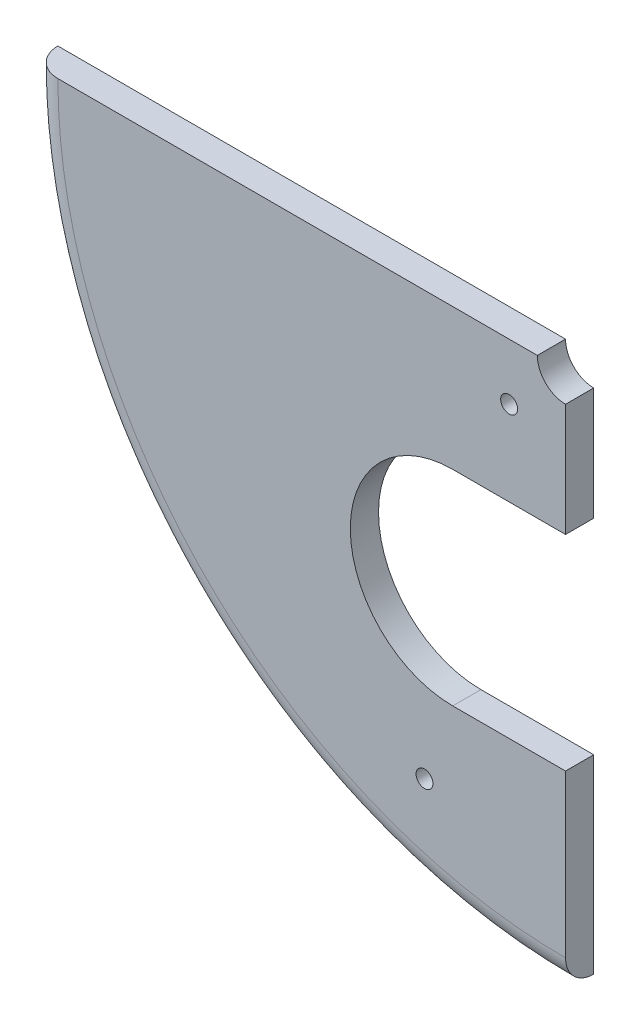
SolidWorks part; units mm, degrees
ref_plane "前基準面" through (0, 0, 0) normal (0, 0, 1) x (1, 0, 0)
ref_plane "上基準面" through (0, 0, 0) normal (0, 1, 0) x (1, 0, 0)
ref_plane "右基準面" through (0, 0, 0) normal (1, 0, 0) x (0, 0, -1)
sketch "草圖1" plane through (0, 0, 0) normal (0, 0, 1) x (1, 0, 0)
  line L0 (-95, 0) -> (-5, 0) construction
  line L1 (-5, 0) -> (-95, 0)
  line L2 (0, -5) -> (0, -95)
  line L3 (95, 0) -> (168.4046, 0) construction
  arc A0 (-95, 0) -> (0, -95) centre (0, 0) ccw
  circle A1 centre (-10, -10) radius 1.5
  arc A3 (-5, 0) -> (0, -5) centre (0, 0) ccw
  circle A4 centre (-25, -75) radius 1.5
  point P16 (0, 0)
  dimension "D1" = 190
  dimension "D2" = 3
  dimension "D9" = 5
  dimension "D4" = 10
  dimension "D8" = 10
extrude "填料-伸長1" add sketch "草圖1" along normal blind 5 contours A1 | A4 | A0 L2 A3 L1 region at (-10, -10, 0) region at (-25, -75, 0)
sketch "草圖2" plane through (0, 0, 0) normal (0, 0, -1) x (-1, 0, 0)
  line L0 (0, -25) -> (0, -61.3121)
  line L3 (-107.2857, 0) -> (167.8844, 0) construction
  line L4 (20, -43.156) -> (0, -43.156) construction
  line L5 (20, -61.3121) -> (0, -61.3121)
  line L6 (20, -25) -> (0, -25)
  arc A2 (20, -61.3121) -> (20, -25) centre (20, -43.156) ccw
  point P2 (0, 35)
  point P15 (0, -35)
  point P20 (0, 0)
  dimension "D1" = 25
extrude "除料-伸長1" cut sketch "草圖2" against normal through all
fillet "圓角2" radius 5 1 edges at (-67.1751, -67.1751, 5)
